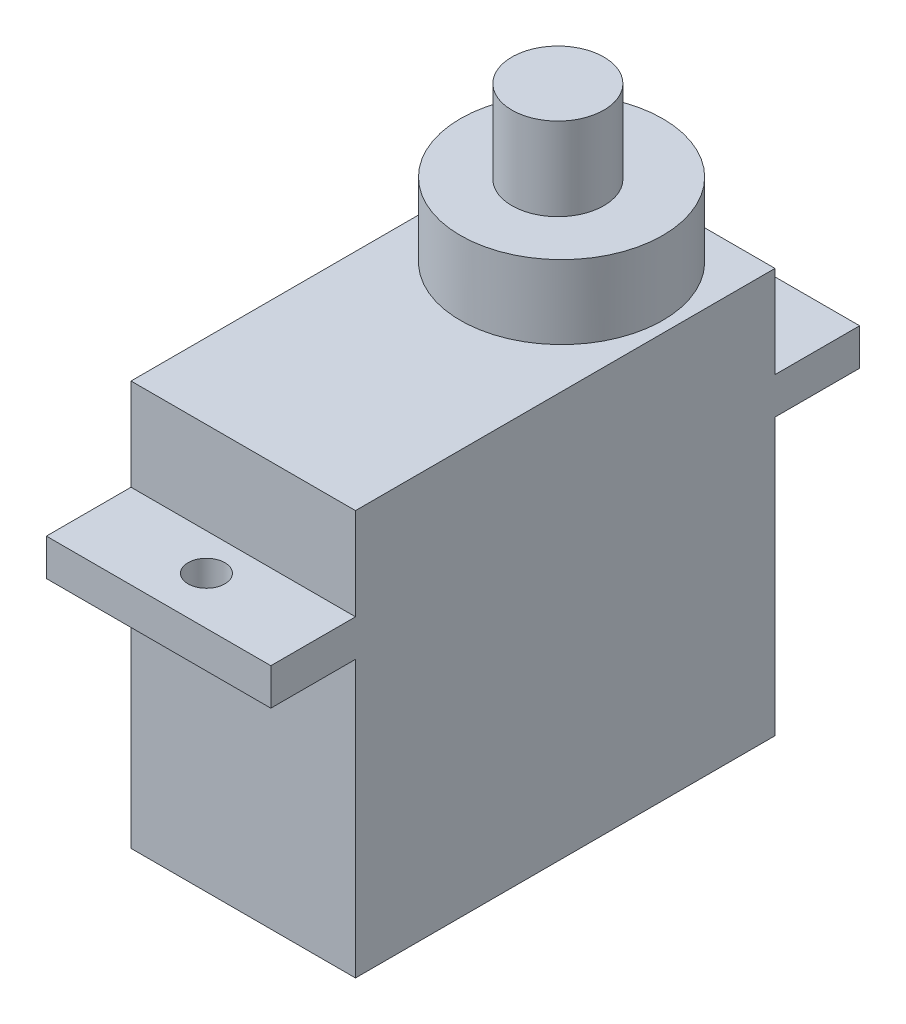
SolidWorks part; units mm, degrees
ref_plane "Front Plane" through (0, 0, 0) normal (0, 0, 1) x (1, 0, 0)
ref_plane "Top Plane" through (0, 0, 0) normal (0, 1, 0) x (1, 0, 0)
ref_plane "Right Plane" through (0, 0, 0) normal (1, 0, 0) x (0, 0, -1)
sketch "Sketch2" plane through (0, 0, 0) normal (0, 1, 0) x (1, 0, 0)
  line L1 (-6.1, -11.4) -> (6.1, -11.4)
  line L2 (-6.1, -11.4) -> (-6.1, 11.4)
  line L3 (-6.1, 11.4) -> (6.1, 11.4)
  line L4 (6.1, -11.4) -> (6.1, 11.4)
  line L5 (-6.1, -11.4) -> (6.1, 11.4) construction
  line L6 (-6.1, 11.4) -> (6.1, -11.4) construction
  point P0 (0, 0)
  dimension "D1" = 22.8
  dimension "D2" = 12.2
extrude "Boss-Extrude1" add sketch "Sketch2" along normal blind 22
ref_plane "Plane1" through (0, 15, 0) normal (0, 1, 0) x (1, 0, 0)
sketch "Sketch3" plane through (0, 15, 0) normal (0, 1, 0) x (1, 0, 0)
  line L0 (0, 11.4) -> (0, 16) construction
  line L1 (6.1, 11.4) -> (-6.1, 11.4) construction
  line L2 (-6.1, 0) -> (6.1, 0) construction
  line L3 (-6.1, 11.4) -> (-6.1, -11.4) construction
  line L4 (6.1, -11.4) -> (6.1, 11.4) construction
  line L5 (-6.1, 11.4) -> (-6.1, 16)
  line L6 (-6.1, 16) -> (6.1, 16)
  line L7 (6.1, 16) -> (6.1, 11.4)
  line L8 (-6.1, 11.4) -> (6.1, 11.4)
  line L9 (-6.1, -11.4) -> (-6.1, -16)
  line L10 (-6.1, -11.4) -> (6.1, -11.4)
  line L11 (6.1, -16) -> (6.1, -11.4)
  line L12 (-6.1, -16) -> (6.1, -16)
  line L13 (0, 11.4) -> (0, 12.4) construction
  circle A0 centre (0, 13.4) radius 1
  circle A1 centre (0, -13.4) radius 1
  dimension "D3" = 2
  dimension "D1" = 4.6
  dimension "D2" = 1
extrude "Boss-Extrude2" add sketch "Sketch3" along normal blind 2
sketch "Sketch4" plane through (0, 22, 0) normal (0, 1, 0) x (1, 0, 0)
  line L0 (0, 16) -> (0, -16) construction
  line L1 (6.1, 16) -> (-6.1, 16) construction
  line L2 (-6.1, -16) -> (6.1, -16) construction
  line L3 (-6.1, 11.4) -> (6.1, 11.4) construction
  line L4 (0, 11.4) -> (0, 5.9) construction
  circle A0 centre (0, 5.9) radius 5.5
  dimension "D1" = 5.5
  dimension "D2" = 11
extrude "Boss-Extrude3" add sketch "Sketch4" along normal blind 4
sketch "Sketch5" plane through (0, 26, 0) normal (0, 1, 0) x (1, 0, 0)
  line L0 (0, 11.4) -> (0, 0) construction
  line L1 (-6.1, 11.4) -> (6.1, 11.4) construction
  circle A0 centre (0, 5.7) radius 2.5
  dimension "D1" = 5
extrude "Boss-Extrude4" add sketch "Sketch5" along normal blind 4.5
